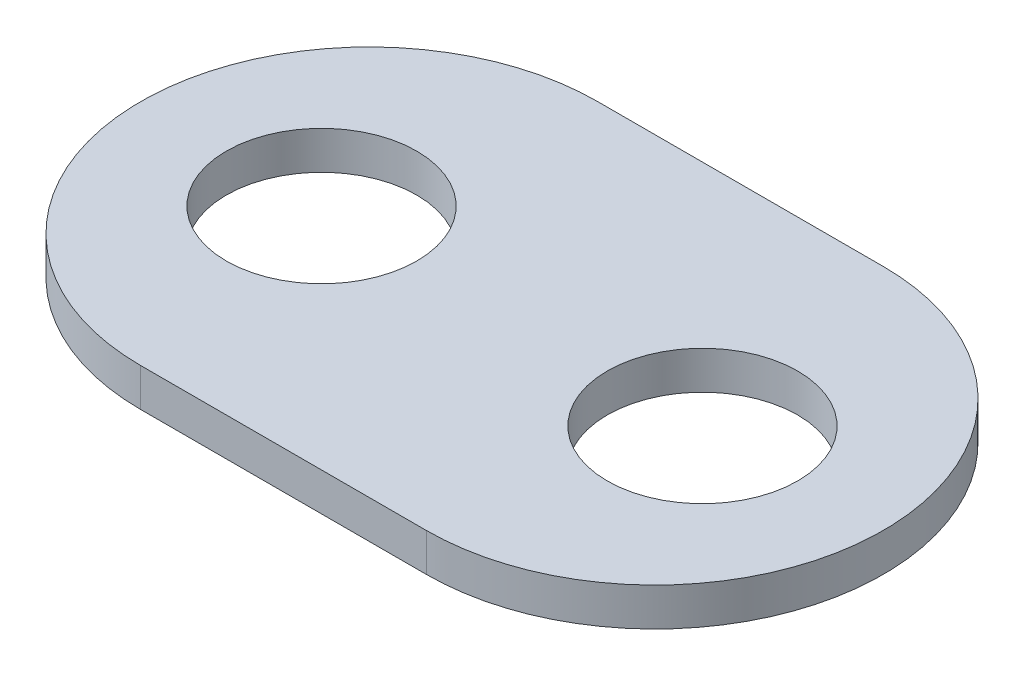
SolidWorks part; units mm, degrees
ref_plane "Front Plane" through (0, 0, 0) normal (0, 0, 1) x (1, 0, 0)
ref_plane "Top Plane" through (0, 0, 0) normal (0, 1, 0) x (1, 0, 0)
ref_plane "Right Plane" through (0, 0, 0) normal (1, 0, 0) x (0, 0, -1)
sketch "Sketch1" plane through (0, 0, 0) normal (0, 1, 0) x (1, 0, 0)
  line L0 (-7.5, -12) -> (7.5, -12)
  line L3 (-7.5, 12) -> (7.5, 12)
  line L4 (-10, 0) -> (10, 0) construction
  circle A2 centre (10, 0) radius 5
  circle A3 centre (-10, 0) radius 5
  circle A4 centre (-10, 0) radius 2.5
  circle A5 centre (10, 0) radius 2.5
  arc A6 (-7.5, 12) -> (-7.5, -12) centre (-7.5, 0) ccw
  arc A7 (7.5, 12) -> (7.5, -12) centre (7.5, 0) cw
  point P6 (0, -12)
  point P15 (0, 0)
  dimension "D3" = 10
  dimension "D4" = 10
  dimension "D5" = 5
  dimension "D6" = 5
  dimension "D7" = 12
  dimension "D10" = 20
  dimension "D2" = 12
  dimension "D8" = 15
  dimension "D9" = 15
  dimension "D11" = 10
extrude "Boss-Extrude1" add sketch "Sketch1" along normal blind 2 contours A3 A2 region at (0, 0, 0)
